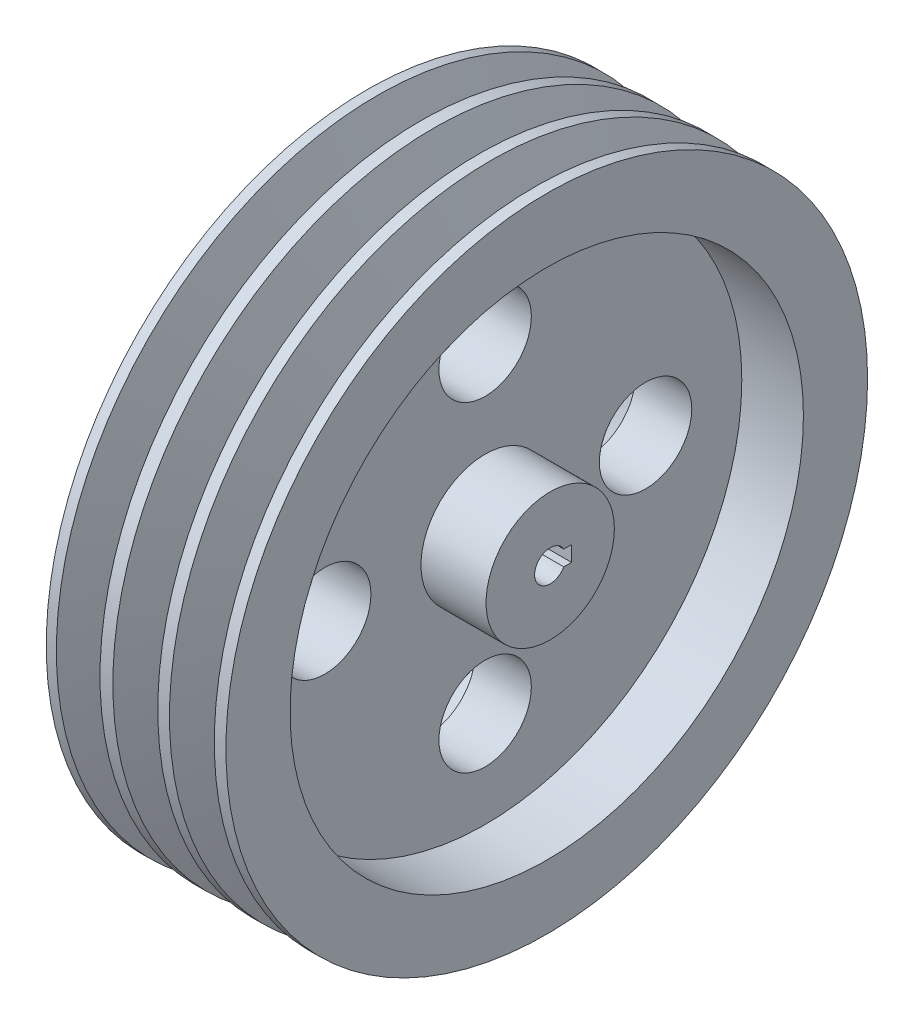
SolidWorks part; units mm, degrees
ref_plane "Front Plane" through (0, 0, 0) normal (0, 0, 1) x (1, 0, 0)
ref_plane "Top Plane" through (0, 0, 0) normal (0, 1, 0) x (1, 0, 0)
ref_plane "Right Plane" through (0, 0, 0) normal (1, 0, 0) x (0, 0, -1)
sketch "Sketch1" plane through (0, 0, 0) normal (0, 1, 0) x (1, 0, 0)
  line L0 (0, 0) -> (0, 25)
  line L1 (70, 0) -> (70, 25)
  line L2 (33.2161, 151.6484) -> (35.6982, -41.6452) construction
  line L3 (24.602, 125) -> (19.602, 125)
  line L4 (2.5976, 125) -> (8.9501, 107)
  line L5 (8.9501, 107) -> (12.8501, 107)
  line L6 (12.8501, 107) -> (19.602, 125)
  line L7 (19.602, 125) -> (24.602, 125)
  line L8 (24.602, 125) -> (31.7228, 107)
  line L9 (31.7228, 107) -> (36.1184, 107)
  line L10 (36.1184, 107) -> (42.1118, 125)
  line L11 (42.1118, 125) -> (46.6528, 125)
  line L12 (53.0899, 107) -> (57.4557, 107)
  line L13 (68.6511, 125) -> (64.122, 125)
  line L14 (68.6511, 125) -> (68.6511, 100)
  line L15 (68.6511, 100) -> (44.6511, 100)
  line L16 (44.6511, 100) -> (44.6511, 80.5)
  line L17 (44.6511, 80.5) -> (22.6511, 80.5)
  line L18 (22.6511, 80.5) -> (22.6511, 100)
  line L19 (-1.3489, 100) -> (22.6511, 100)
  line L21 (0, 6.0832) -> (70, 6.0832)
  line L23 (70, 0) -> (0, 0) construction
  line L24 (0, 14.5) -> (70, 14.5)
  line L25 (2.5976, 125) -> (-1.3489, 125)
  line L26 (44.6511, 25) -> (70, 25)
  line L29 (22.6511, 25) -> (0, 25)
  line L31 (22.6511, 80.5) -> (22.6511, 25)
  line L32 (44.6511, 25) -> (44.6511, 80.5)
  line L33 (-1.3489, 100) -> (-1.3489, 125)
  line L34 (22.6511, 44.5) -> (44.6511, 44.5)
  line L35 (46.6528, 125) -> (53.0899, 107)
  line L36 (64.122, 125) -> (57.4557, 107)
  point P7 (37.4103, 107.6469)
  point P32 (31.7228, 107.6469)
  point P36 (-143.0523, 139.7738)
  point P37 (0, 0)
  dimension "D1" = 24
  dimension "D2" = 70
  dimension "D3" = 24
  dimension "D4" = 36
  dimension "D5" = 14.5
  dimension "D6" = 25
  dimension "D7" = 125
  dimension "D8" = 22
  dimension "D9" = 25
  dimension "D10" = 18
  dimension "D11" = 75
  dimension "D12" = 19.5
  dimension "25" = 25
  dimension "D13" = 40
  dimension "D14" = 40
  dimension "D15" = 19.5
  dimension "D19" = 40
revolve "Revolve2" add sketch "Sketch1" angle 360 about L23 region at (35, 0, -10.2916) region at (34.5029, 0, -25.2784) region at (33.6511, 0, -62.5) region at (33.6566, 0, -104.5841)
sketch "Sketch4" plane through (70, 0, 0) normal (1, 0, 0) x (0, 0, -1)
  line L0 (8.292, -3) -> (5.292, -3)
  line L1 (5.292, -3) -> (5.292, 3)
  line L2 (5.292, 3) -> (8.292, 3)
  line L3 (8.292, 3) -> (8.292, -3)
  circle A0 centre (0, 0) radius 62.5
  circle A1 centre (0, 62.5) radius 18
  circle A2 centre (62.5, 0) radius 18
  circle A3 centre (0, -62.5) radius 18
  circle A4 centre (-62.5, 0) radius 18
  circle A5 centre (0, 0) radius 6.0832 construction
  point P14 (0, 0)
  circle M11 centre (0, 0) radius 6.0832
  dimension "D1" = 4
  dimension "D2" = 36
  dimension "D3" = 125
  dimension "D4" = 6
  dimension "D5" = 3
  dimension "D6" = 3
extrude "Cut-Extrude2" cut sketch "Sketch4" against normal through all contours L3 L2 L0 M11 | A0 A2 | A0 A2 | A0 A1 | A0 A1 | A0 A4 | A0 A3 | A0 A3 | A0 A4 region at (70, 0, -7.0483) region at (70, 0, -54.413) region at (70, 0, -69.6536) region at (70, 54.413, 0) region at (70, 69.6536, 0) region at (70, -69.6536, 0) region at (70, -54.413, 0) region at (70, 0, 54.413) region at (70, 0, 69.6536)
